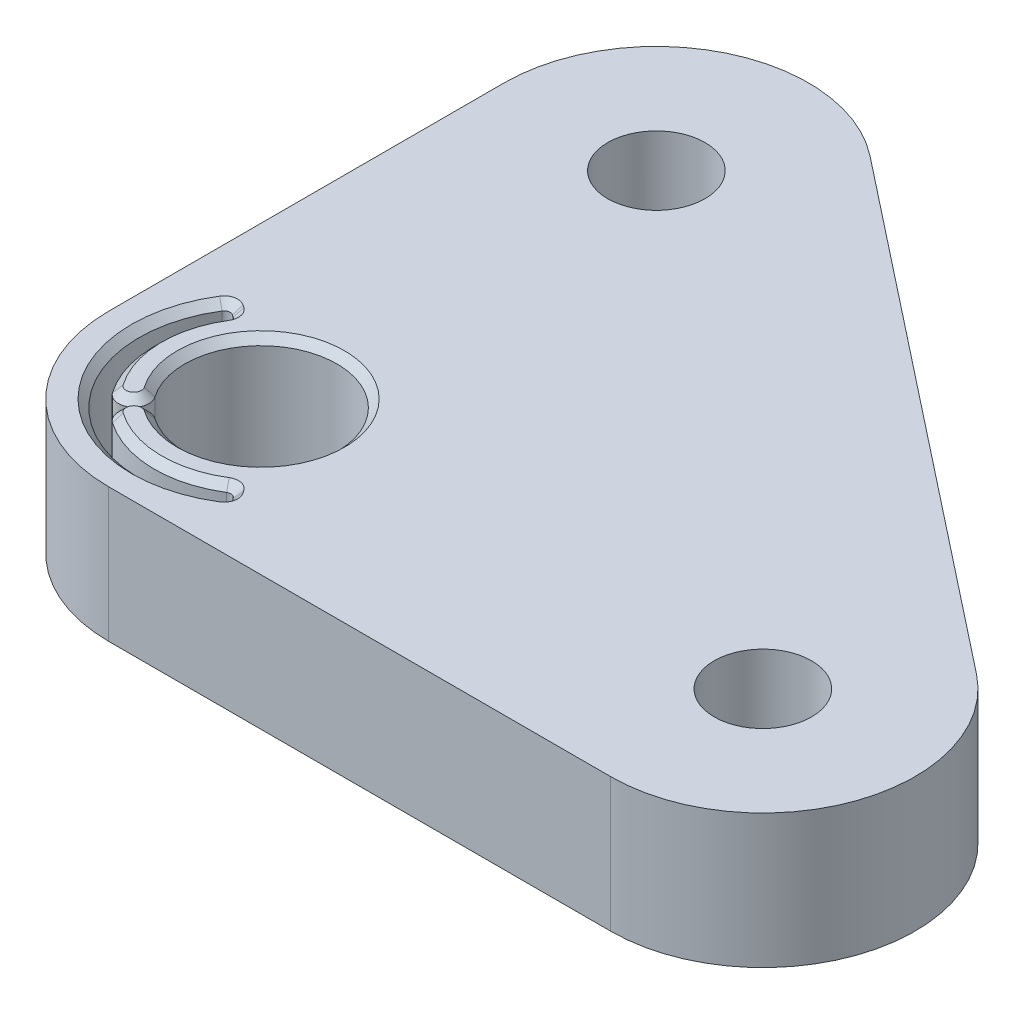
SolidWorks part; units mm, degrees
ref_plane "Front" through (0, 0, 0) normal (0, 0, 1) x (1, 0, 0)
ref_plane "Top" through (0, 0, 0) normal (0, 1, 0) x (1, 0, 0)
ref_plane "Right" through (0, 0, 0) normal (1, 0, 0) x (0, 0, -1)
sketch "Sketch1" plane through (0, 0, 0) normal (0, 1, 0) x (1, 0, 0)
  line L0 (0, 0) -> (16.5, 0) construction
  line L1 (16.5, 0) -> (0, 13) construction
  line L2 (0, 13) -> (0, 0) construction
  line L3 (-5, -5) -> (30.9254, -5)
  line L4 (30.9254, -5) -> (-5, 23.3048)
  line L5 (-5, 23.3048) -> (-5, -5)
  circle A0 centre (16.5, 0) radius 1.6
  circle A1 centre (0, 0) radius 2.5
  circle A2 centre (0, 13) radius 1.6
  dimension "D3" = 5
  dimension "D4" = 3.2
  dimension "D1" = 16.5
  dimension "D2" = 13
  dimension "D5" = 5
extrude "Boss-Extrude1" add sketch "Sketch1" along normal blind 1.57
fillet "Fillet1" radius 5 3 edges at (-5, 0.785, -23.3048) (-5, 0.785, 5) (30.9254, 0.785, 5)
other "Move Face1" [suppressed] offset 0.0762 parameters "D1"=0.0762
sketch "Sketch2" plane through (0, 1.57, 0) normal (0, 1, 0) x (1, 0, 0)
  line L3 (19.5944, 3.9275) -> (3.0944, 16.9275)
  line L4 (-5, 13) -> (-5, 0)
  line L5 (0, -5) -> (16.5, -5)
  line L6 (19.5944, 3.9275) -> (3.0944, 16.9275)
  line L7 (-5, 13) -> (-5, 0)
  line L8 (0, -5) -> (16.5, -5)
  circle A0 centre (0, 0) radius 2.5 construction
  circle A1 centre (16.5, 0) radius 1.6 construction
  circle A2 centre (0, 13) radius 1.6 construction
  arc A3 (3.0944, 16.9275) -> (-5, 13) centre (0, 13) ccw
  arc A4 (-5, 0) -> (0, -5) centre (0, 0) ccw
  arc A5 (16.5, -5) -> (19.5944, 3.9275) centre (16.5, 0) ccw
  arc A6 (3.0944, 16.9275) -> (-5, 13) centre (0, 13) ccw
  arc A7 (-5, 0) -> (0, -5) centre (0, 0) ccw
  arc A8 (16.5, -5) -> (19.5944, 3.9275) centre (16.5, 0) ccw
  circle A9 centre (0, 0) radius 2.5
  circle A10 centre (16.5, 0) radius 1.6
  circle A11 centre (0, 13) radius 1.6
  dimension "D1" = 0
extrude "Boss-Extrude2" add sketch "Sketch2" along normal blind 2.83
sketch "Sketch3" plane through (0, 0, 0) normal (0, -1, 0) x (1, 0, 0)
  circle A0 centre (16.5, 0) radius 3
  circle A1 centre (0, -13) radius 3
  circle A2 centre (0, -13) radius 1.6 construction
  circle A3 centre (16.5, 0) radius 1.6 construction
  circle A4 centre (0, -13) radius 1.6
  circle A5 centre (16.5, 0) radius 1.6
  dimension "D1" = 6
extrude "Boss-Extrude3" add sketch "Sketch3" along normal blind 0.6
sketch "Sketch4" plane through (0, 4.4, 0) normal (0, 1, 0) x (1, 0, 0)
  line B0 (1.7207, -2.4575) -> (0, 0) construction
  line B1 (2.1191, -3.0264) -> (2.1766, -3.1085)
  line B2 (-3.0264, 2.1191) -> (-3.1085, 2.1766)
  line B3 (-1.7207, -2.4575) -> (0, 0) construction
  arc B4 (2.1187, -3.3928) -> (-3.3928, 2.1187) centre (0, 0) cw
  arc B5 (-1.4339, -2.0479) -> (-2.0075, -2.867) centre (-1.7207, -2.4575) ccw
  arc B6 (-2.0075, -2.867) -> (1.8496, -2.9714) centre (0, 0) ccw
  arc B7 (-2.867, -2.0075) -> (-2.9714, 1.8496) centre (0, 0) cw
  arc B8 (-2.0479, -1.4339) -> (-2.867, -2.0075) centre (-2.4575, -1.7207) cw
  arc B9 (-1.4339, -2.0479) -> (-2.0479, -1.4339) centre (0, 0) cw
  arc B10 (2.1191, -3.0264) -> (1.8496, -2.9714) centre (1.9553, -3.1411) ccw
  arc B11 (2.1766, -3.1085) -> (2.1187, -3.3928) centre (2.0127, -3.2232) cw
  arc B12 (-3.1085, 2.1766) -> (-3.3928, 2.1187) centre (-3.2232, 2.0127) ccw
  arc B13 (-3.0264, 2.1191) -> (-2.9714, 1.8496) centre (-3.1411, 1.9553) cw
sketch_block_instance "5mm_bore_flexure_relief-1"
sketch_block "5mm_bore_flexure_relief" parameters "D4"=2.5, "D6"=0.2, "D1"=80, "D2"=0.5, "D3"=70, "D5"=1
extrude "Cut-Extrude1" cut sketch "Sketch4" against normal blind 10
sketch "Sketch5" plane through (9.4139, 0, -11.9484) normal (0.6189, 0, -0.7855) x (-0.7855, 0, -0.6189)
  line L0 (-12.9606, 0.6) -> (8.0453, 0.6) construction
  line L1 (-12.9606, 4.4) -> (-12.9606, 0) construction
  line L2 (8.0453, 0) -> (8.0453, 4.4) construction
  line L3 (-12.9606, 0) -> (8.0453, 0) construction
  text T0 "LCR-02" font "Century Gothic" height in points 12
  dimension "D1" = 0.6
extrude "Part Num Left" cut sketch "Sketch5" against normal blind 0.4
chamfer "Chamfer1" distance 0.6 angle 45 2 edges at (0, 0, -10) (16.5, 0, 3)
chamfer "Chamfer2" distance 0.25 angle 45 12 edges at (-2.8284, 4.4, 2.8284) (2.2087, 4.4, 3.2631) (-3.2631, 4.4, -2.2087) (2.1478, 4.4, 3.0674) (-3.0674, 4.4, -2.1478) (1.9953, 4.4, 2.9452) (-2.9452, 4.4, -1.9953) (-0.0946, 4.4, 3.4987) (-3.4987, 4.4, 0.0946) (-2.1303, 4.4, 2.1707) (-2.1707, 4.4, 2.1303) (1.7678, 4.4, -1.7678)
mirror "Mirror1" [suppressed] of bodies 106 104
delete or keep bodies "Body-Delete/Keep 1" [suppressed] type keep bodies bodies 105
sketch "Sketch6" [suppressed] plane through (-13.2439, 0, -16.8096) normal (-0.6189, 0, -0.7855) x (-0.7855, 0, 0.6189)
  line L0 (-0.1904, 0.6) -> (20.8155, 0.6) construction
  line L1 (-0.1904, 0) -> (-0.1904, 4.4) construction
  line L2 (20.8155, 4.4) -> (20.8155, 0) construction
  line L3 (20.8155, 0) -> (-0.1904, 0) construction
  text T0 "RCR-01" font "Century Gothic" height in points 12
  dimension "D1" = 0.6
extrude "Part Num Right" [suppressed] cut sketch "Sketch6" against normal blind 0.4
